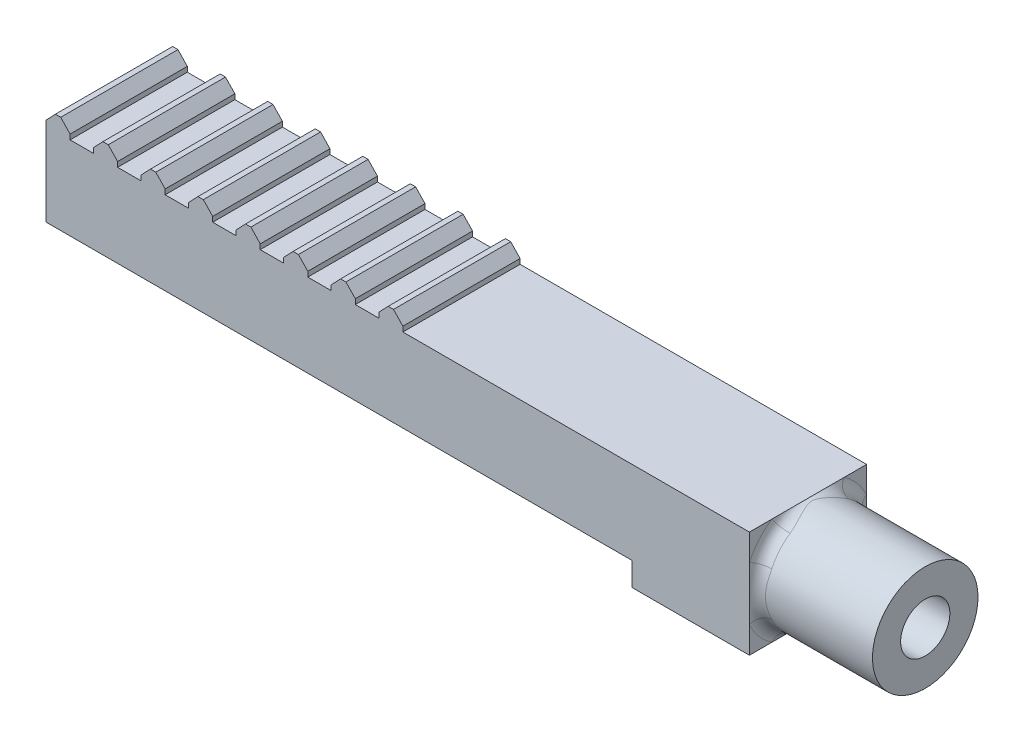
SolidWorks part; units mm, degrees
ref_plane "Front Plane" through (0, 0, 0) normal (0, 0, 1) x (1, 0, 0)
ref_plane "Top Plane" through (0, 0, 0) normal (0, 1, 0) x (1, 0, 0)
ref_plane "Right Plane" through (0, 0, 0) normal (1, 0, 0) x (0, 0, -1)
sketch "Sketch1" plane through (0, 0, 0) normal (0, 1, 0) x (1, 0, 0)
  line L1 (0, 0) -> (60, 0)
  line L2 (0, 0) -> (0, -10)
  line L3 (0, -10) -> (60, -10)
  line L4 (60, 0) -> (60, -10)
  dimension "D1" = 10
  dimension "D2" = 60
extrude "Boss-Extrude1" add sketch "Sketch1" along normal blind 12
sketch "Sketch2" plane through (0, 0, 10) normal (0, 0, 1) x (1, 0, 0)
  line L0 (6.1101, 12) -> (6.1101, 12.431)
  line L1 (5.3101, 13.2707) -> (6.1101, 12.431)
  line L2 (4.855, 13.2707) -> (5.3101, 13.2707)
  line L3 (4.055, 12.431) -> (4.855, 13.2707)
  line L4 (4.055, 12.431) -> (4.055, 12)
  line L5 (4.055, 12) -> (6.1101, 12)
  line L6 (10.1651, 12) -> (10.1651, 12.431)
  line L7 (9.3651, 13.2707) -> (10.1651, 12.431)
  line L8 (8.9101, 13.2707) -> (9.3651, 13.2707)
  line L9 (8.1101, 12.431) -> (8.9101, 13.2707)
  line L10 (8.1101, 12.431) -> (8.1101, 12)
  line L11 (8.1101, 12) -> (10.1651, 12)
  line L12 (14.2201, 12) -> (14.2201, 12.431)
  line L13 (13.4201, 13.2707) -> (14.2201, 12.431)
  line L14 (12.9651, 13.2707) -> (13.4201, 13.2707)
  line L15 (12.1651, 12.431) -> (12.9651, 13.2707)
  line L16 (12.1651, 12.431) -> (12.1651, 12)
  line L17 (12.1651, 12) -> (14.2201, 12)
  line L18 (18.2751, 12) -> (18.2751, 12.431)
  line L19 (17.4751, 13.2707) -> (18.2751, 12.431)
  line L20 (17.0201, 13.2707) -> (17.4751, 13.2707)
  line L21 (16.2201, 12.431) -> (17.0201, 13.2707)
  line L22 (16.2201, 12.431) -> (16.2201, 12)
  line L23 (16.2201, 12) -> (18.2751, 12)
  line L24 (22.3302, 12) -> (22.3302, 12.431)
  line L25 (21.5302, 13.2707) -> (22.3302, 12.431)
  line L26 (21.0751, 13.2707) -> (21.5302, 13.2707)
  line L27 (20.2751, 12.431) -> (21.0751, 13.2707)
  line L28 (20.2751, 12.431) -> (20.2751, 12)
  line L29 (20.2751, 12) -> (22.3302, 12)
  line L30 (26.3852, 12) -> (26.3852, 12.431)
  line L31 (25.5852, 13.2707) -> (26.3852, 12.431)
  line L32 (25.1302, 13.2707) -> (25.5852, 13.2707)
  line L33 (24.3302, 12.431) -> (25.1302, 13.2707)
  line L34 (24.3302, 12.431) -> (24.3302, 12)
  line L35 (24.3302, 12) -> (26.3852, 12)
  line L36 (30.4402, 12) -> (30.4402, 12.431)
  line L37 (29.6402, 13.2707) -> (30.4402, 12.431)
  line L38 (29.1852, 13.2707) -> (29.6402, 13.2707)
  line L39 (28.3852, 12.431) -> (29.1852, 13.2707)
  line L40 (28.3852, 12.431) -> (28.3852, 12)
  line L41 (28.3852, 12) -> (30.4402, 12)
  line L90 (0, 12) -> (2.055, 12)
  line L91 (0, 12) -> (60, 12) construction
  line L92 (0, 12.431) -> (0.8, 13.2707)
  line L93 (0.8, 13.2707) -> (1.255, 13.2707)
  line L94 (1.255, 13.2707) -> (2.055, 12.431)
  line L95 (2.055, 11.569) -> (2.055, 12) construction
  line L96 (0, 12) -> (0, 11.569) construction
  line L265 (0, 12.431) -> (0, 12)
  line L266 (0, 11.569) -> (0.8, 10.7293) construction
  line L267 (0.8, 10.7293) -> (1.255, 10.7293) construction
  line L268 (1.255, 10.7293) -> (2.055, 11.569) construction
  line L269 (2.055, 12) -> (2.055, 12.431)
  dimension "D1" = 0.431
  dimension "D2" = 2.055
  dimension "D3" = 1.2707
  dimension "D4" = 0.8
  dimension "D5" = 0.8
  dimension "D6" = 0.431
  dimension "D8" = 2
  dimension "D7" = 8
extrude "Boss-Extrude2" add sketch "Sketch2" against normal up to surface (10 mm away) up to face at (30, 6, 0)
sketch "Sketch3" plane through (0, 0, 0) normal (0, 0, -1) x (-1, 0, 0)
  line L0 (-60, 12) -> (-60, 0) construction
  line L1 (-60, 9) -> (0, 9)
  line L2 (-60, 9) -> (-60, 0)
  line L3 (-60, 0) -> (0, 0)
  line L4 (0, 9) -> (0, 0)
  line L5 (0, 12.431) -> (0, 0) construction
  line L6 (-60, 0) -> (0, 0) construction
  line L7 (-60, 12) -> (-30.4402, 12) construction
  dimension "D1" = 3
extrude "Cut-Extrude1" cut sketch "Sketch3" against normal through all
sketch "Sketch4" plane through (0, 9, 0) normal (0, -1, 0) x (1, 0, 0)
  line L0 (0, 10) -> (60, 10) construction
  line L1 (60, 10) -> (32.2775, 10)
  line L2 (60, 10) -> (60, 0)
  line L3 (60, 0) -> (32.2775, 0)
  line L4 (32.2775, 10) -> (32.2775, 0)
  line L5 (60, 10) -> (60, 0) construction
  line L6 (0, 0) -> (60, 0) construction
sketch "Sketch8" plane through (0, 9, 0) normal (0, -1, 0) x (1, 0, 0)
  line L4 (0, 0) -> (60, 0)
  line L5 (60, 0) -> (60, 10)
  line L6 (60, 10) -> (0, 10)
  line L7 (0, 10) -> (0, 0)
  line L8 (0, 0) -> (60, 0)
  line L9 (60, 0) -> (60, 10)
  line L10 (60, 10) -> (0, 10)
  line L11 (0, 10) -> (0, 0)
  dimension "D1" = 0
extrude "Boss-Extrude7" add sketch "Sketch8" along normal up to surface (6.1 mm away)
sketch "Sketch9" plane through (60, 0, 0) normal (1, 0, 0) x (0, 0, -1)
  line L0 (0, 12) -> (0, 2.9) construction
  line L1 (-10, 2.9) -> (0, 2.9) construction
  circle A0 centre (-5, 7.45) radius 2.1
  circle A1 centre (-5, 7.45) radius 4.5
  point P5 (0, 7.45)
  point P9 (-5, 2.9)
  dimension "D1" = 4.2
  dimension "D2" = 9
extrude "Boss-Extrude8" add sketch "Sketch9" along normal blind 10
fillet "Fillet1" radius 1 1 edges at (60, 7.45, 9.5)
sketch "Sketch10" plane through (0, 0, 10) normal (0, 0, 1) x (1, 0, 0)
  line L0 (60, 2.9) -> (60, 5.1587) construction
  line L1 (0, 2.9) -> (50, 2.9)
  line L2 (0, 2.9) -> (0, 3.9)
  line L3 (0, 3.9) -> (50, 3.9)
  line L4 (50, 2.9) -> (50, 3.9)
  dimension "D1" = 1
  dimension "D2" = 10
extrude "Cut-Extrude2" cut sketch "Sketch10" against normal blind 10
sketch "Sketch11" plane through (0, 0, 10) normal (0, 0, 1) x (1, 0, 0)
  line L0 (50, 2.9) -> (50, 3.9) construction
  line L1 (0, 3.9) -> (50, 3.9)
  line L2 (0, 3.9) -> (0, 4.9)
  line L3 (0, 4.9) -> (50, 4.9)
  line L4 (50, 3.9) -> (50, 4.9)
  dimension "D1" = 1
extrude "Cut-Extrude3" cut sketch "Sketch11" against normal blind 10
